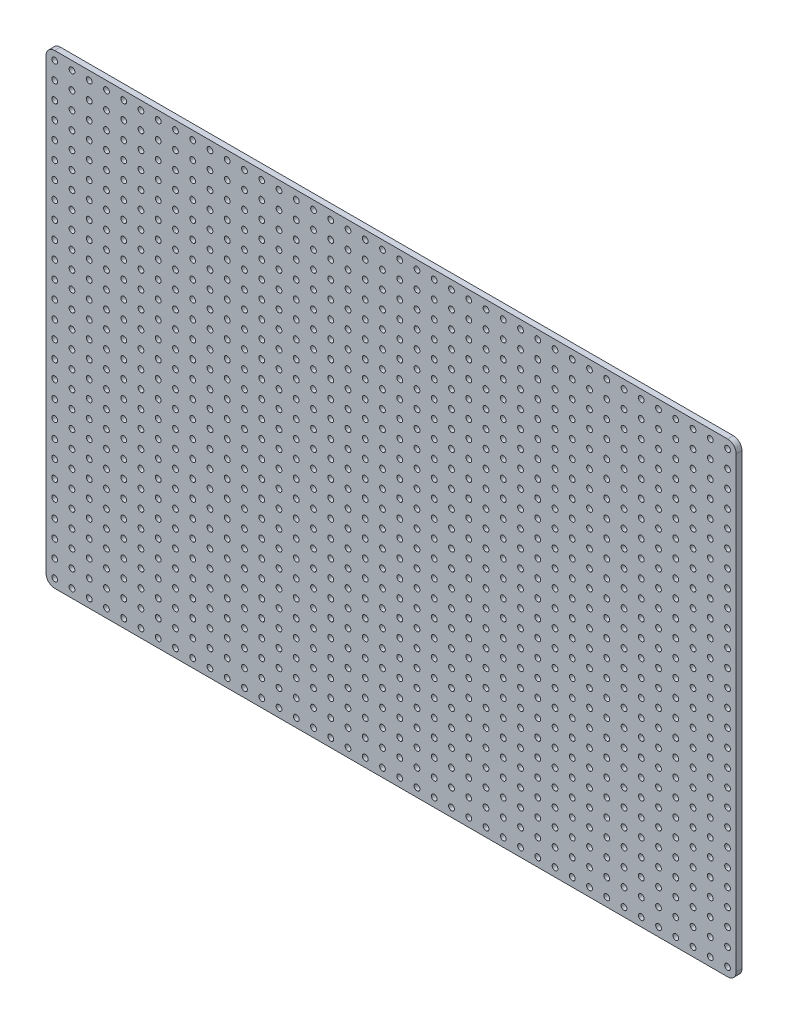
SolidWorks part; units mm, degrees
ref_plane "Alzado" through (0, 0, 0) normal (0, 0, 1) x (1, 0, 0)
ref_plane "Planta" through (0, 0, 0) normal (0, 1, 0) x (1, 0, 0)
ref_plane "Vista lateral" through (0, 0, 0) normal (1, 0, 0) x (0, 0, -1)
sketch "Model" plane through (0, 0, 0) normal (0, 0, 1) x (1, 0, 0)
  line L0 (256.4291, 489.7422) -> (607.4291, 489.7422)
  line L1 (256.4291, 246.7422) -> (607.4291, 246.7422)
  line L2 (251.9291, 251.2422) -> (251.9291, 485.2422)
  line L3 (611.9291, 485.2422) -> (611.9291, 251.2422)
  arc A0 (611.9291, 485.2422) -> (607.4291, 489.7422) centre (607.4291, 485.2422) ccw
  arc A1 (256.4291, 489.7422) -> (251.9291, 485.2422) centre (256.4291, 485.2422) ccw
  arc A2 (607.4291, 246.7422) -> (611.9291, 251.2422) centre (607.4291, 251.2422) ccw
  arc A3 (251.9291, 251.2422) -> (256.4291, 246.7422) centre (256.4291, 251.2422) ccw
  circle A4 centre (256.4291, 485.2422) radius 1.5
  circle A5 centre (256.4291, 476.2422) radius 1.5
  circle A6 centre (256.4291, 467.2422) radius 1.5
  circle A7 centre (256.4291, 458.2422) radius 1.5
  circle A8 centre (256.4291, 449.2422) radius 1.5
  circle A9 centre (256.4291, 440.2422) radius 1.5
  circle A10 centre (256.4291, 431.2422) radius 1.5
  circle A11 centre (256.4291, 422.2422) radius 1.5
  circle A12 centre (256.4291, 413.2422) radius 1.5
  circle A13 centre (256.4291, 404.2422) radius 1.5
  circle A14 centre (256.4291, 395.2422) radius 1.5
  circle A15 centre (256.4291, 386.2422) radius 1.5
  circle A16 centre (256.4291, 377.2422) radius 1.5
  circle A17 centre (256.4291, 368.2422) radius 1.5
  circle A18 centre (256.4291, 359.2422) radius 1.5
  circle A19 centre (256.4291, 350.2422) radius 1.5
  circle A20 centre (256.4291, 341.2422) radius 1.5
  circle A21 centre (256.4291, 332.2422) radius 1.5
  circle A22 centre (256.4291, 323.2422) radius 1.5
  circle A23 centre (256.4291, 314.2422) radius 1.5
  circle A24 centre (256.4291, 305.2422) radius 1.5
  circle A25 centre (265.4291, 485.2422) radius 1.5
  circle A26 centre (265.4291, 476.2422) radius 1.5
  circle A27 centre (265.4291, 467.2422) radius 1.5
  circle A28 centre (265.4291, 458.2422) radius 1.5
  circle A29 centre (265.4291, 449.2422) radius 1.5
  circle A30 centre (265.4291, 440.2422) radius 1.5
  circle A31 centre (265.4291, 431.2422) radius 1.5
  circle A32 centre (265.4291, 422.2422) radius 1.5
  circle A33 centre (265.4291, 413.2422) radius 1.5
  circle A34 centre (265.4291, 404.2422) radius 1.5
  circle A35 centre (265.4291, 395.2422) radius 1.5
  circle A36 centre (265.4291, 386.2422) radius 1.5
  circle A37 centre (265.4291, 377.2422) radius 1.5
  circle A38 centre (265.4291, 368.2422) radius 1.5
  circle A39 centre (265.4291, 359.2422) radius 1.5
  circle A40 centre (265.4291, 350.2422) radius 1.5
  circle A41 centre (265.4291, 341.2422) radius 1.5
  circle A42 centre (265.4291, 332.2422) radius 1.5
  circle A43 centre (265.4291, 323.2422) radius 1.5
  circle A44 centre (265.4291, 314.2422) radius 1.5
  circle A45 centre (265.4291, 305.2422) radius 1.5
  circle A46 centre (274.4291, 485.2422) radius 1.5
  circle A47 centre (274.4291, 476.2422) radius 1.5
  circle A48 centre (274.4291, 467.2422) radius 1.5
  circle A49 centre (274.4291, 458.2422) radius 1.5
  circle A50 centre (274.4291, 449.2422) radius 1.5
  circle A51 centre (274.4291, 440.2422) radius 1.5
  circle A52 centre (274.4291, 431.2422) radius 1.5
  circle A53 centre (274.4291, 422.2422) radius 1.5
  circle A54 centre (274.4291, 413.2422) radius 1.5
  circle A55 centre (274.4291, 404.2422) radius 1.5
  circle A56 centre (274.4291, 395.2422) radius 1.5
  circle A57 centre (274.4291, 386.2422) radius 1.5
  circle A58 centre (274.4291, 377.2422) radius 1.5
  circle A59 centre (274.4291, 368.2422) radius 1.5
  circle A60 centre (274.4291, 359.2422) radius 1.5
  circle A61 centre (274.4291, 350.2422) radius 1.5
  circle A62 centre (274.4291, 341.2422) radius 1.5
  circle A63 centre (274.4291, 332.2422) radius 1.5
  circle A64 centre (274.4291, 323.2422) radius 1.5
  circle A65 centre (274.4291, 314.2422) radius 1.5
  circle A66 centre (274.4291, 305.2422) radius 1.5
  circle A67 centre (283.4291, 485.2422) radius 1.5
  circle A68 centre (283.4291, 476.2422) radius 1.5
  circle A69 centre (283.4291, 467.2422) radius 1.5
  circle A70 centre (283.4291, 458.2422) radius 1.5
  circle A71 centre (283.4291, 449.2422) radius 1.5
  circle A72 centre (283.4291, 440.2422) radius 1.5
  circle A73 centre (283.4291, 431.2422) radius 1.5
  circle A74 centre (283.4291, 422.2422) radius 1.5
  circle A75 centre (283.4291, 413.2422) radius 1.5
  circle A76 centre (283.4291, 404.2422) radius 1.5
  circle A77 centre (283.4291, 395.2422) radius 1.5
  circle A78 centre (283.4291, 386.2422) radius 1.5
  circle A79 centre (283.4291, 377.2422) radius 1.5
  circle A80 centre (283.4291, 368.2422) radius 1.5
  circle A81 centre (283.4291, 359.2422) radius 1.5
  circle A82 centre (283.4291, 350.2422) radius 1.5
  circle A83 centre (283.4291, 341.2422) radius 1.5
  circle A84 centre (283.4291, 332.2422) radius 1.5
  circle A85 centre (283.4291, 323.2422) radius 1.5
  circle A86 centre (283.4291, 314.2422) radius 1.5
  circle A87 centre (283.4291, 305.2422) radius 1.5
  circle A88 centre (292.4291, 485.2422) radius 1.5
  circle A89 centre (292.4291, 476.2422) radius 1.5
  circle A90 centre (292.4291, 467.2422) radius 1.5
  circle A91 centre (292.4291, 458.2422) radius 1.5
  circle A92 centre (292.4291, 449.2422) radius 1.5
  circle A93 centre (292.4291, 440.2422) radius 1.5
  circle A94 centre (292.4291, 431.2422) radius 1.5
  circle A95 centre (292.4291, 422.2422) radius 1.5
  circle A96 centre (292.4291, 413.2422) radius 1.5
  circle A97 centre (292.4291, 404.2422) radius 1.5
  circle A98 centre (292.4291, 395.2422) radius 1.5
  circle A99 centre (292.4291, 386.2422) radius 1.5
  circle A100 centre (292.4291, 377.2422) radius 1.5
  circle A101 centre (292.4291, 368.2422) radius 1.5
  circle A102 centre (292.4291, 359.2422) radius 1.5
  circle A103 centre (292.4291, 350.2422) radius 1.5
  circle A104 centre (292.4291, 341.2422) radius 1.5
  circle A105 centre (292.4291, 332.2422) radius 1.5
  circle A106 centre (292.4291, 323.2422) radius 1.5
  circle A107 centre (292.4291, 314.2422) radius 1.5
  circle A108 centre (292.4291, 305.2422) radius 1.5
  circle A109 centre (301.4291, 485.2422) radius 1.5
  circle A110 centre (301.4291, 476.2422) radius 1.5
  circle A111 centre (301.4291, 467.2422) radius 1.5
  circle A112 centre (301.4291, 458.2422) radius 1.5
  circle A113 centre (301.4291, 449.2422) radius 1.5
  circle A114 centre (301.4291, 440.2422) radius 1.5
  circle A115 centre (301.4291, 431.2422) radius 1.5
  circle A116 centre (301.4291, 422.2422) radius 1.5
  circle A117 centre (301.4291, 413.2422) radius 1.5
  circle A118 centre (301.4291, 404.2422) radius 1.5
  circle A119 centre (301.4291, 395.2422) radius 1.5
  circle A120 centre (301.4291, 386.2422) radius 1.5
  circle A121 centre (301.4291, 377.2422) radius 1.5
  circle A122 centre (301.4291, 368.2422) radius 1.5
  circle A123 centre (301.4291, 359.2422) radius 1.5
  circle A124 centre (301.4291, 350.2422) radius 1.5
  circle A125 centre (301.4291, 341.2422) radius 1.5
  circle A126 centre (301.4291, 332.2422) radius 1.5
  circle A127 centre (301.4291, 323.2422) radius 1.5
  circle A128 centre (301.4291, 314.2422) radius 1.5
  circle A129 centre (301.4291, 305.2422) radius 1.5
  circle A130 centre (310.4291, 485.2422) radius 1.5
  circle A131 centre (310.4291, 476.2422) radius 1.5
  circle A132 centre (310.4291, 467.2422) radius 1.5
  circle A133 centre (310.4291, 458.2422) radius 1.5
  circle A134 centre (310.4291, 449.2422) radius 1.5
  circle A135 centre (310.4291, 440.2422) radius 1.5
  circle A136 centre (310.4291, 431.2422) radius 1.5
  circle A137 centre (310.4291, 422.2422) radius 1.5
  circle A138 centre (310.4291, 413.2422) radius 1.5
  circle A139 centre (310.4291, 404.2422) radius 1.5
  circle A140 centre (310.4291, 395.2422) radius 1.5
  circle A141 centre (310.4291, 386.2422) radius 1.5
  circle A142 centre (310.4291, 377.2422) radius 1.5
  circle A143 centre (310.4291, 368.2422) radius 1.5
  circle A144 centre (310.4291, 359.2422) radius 1.5
  circle A145 centre (310.4291, 350.2422) radius 1.5
  circle A146 centre (310.4291, 341.2422) radius 1.5
  circle A147 centre (310.4291, 332.2422) radius 1.5
  circle A148 centre (310.4291, 323.2422) radius 1.5
  circle A149 centre (310.4291, 314.2422) radius 1.5
  circle A150 centre (310.4291, 305.2422) radius 1.5
  circle A151 centre (319.4291, 485.2422) radius 1.5
  circle A152 centre (319.4291, 476.2422) radius 1.5
  circle A153 centre (319.4291, 467.2422) radius 1.5
  circle A154 centre (319.4291, 458.2422) radius 1.5
  circle A155 centre (319.4291, 449.2422) radius 1.5
  circle A156 centre (319.4291, 440.2422) radius 1.5
  circle A157 centre (319.4291, 431.2422) radius 1.5
  circle A158 centre (319.4291, 422.2422) radius 1.5
  circle A159 centre (319.4291, 413.2422) radius 1.5
  circle A160 centre (319.4291, 404.2422) radius 1.5
  circle A161 centre (319.4291, 395.2422) radius 1.5
  circle A162 centre (319.4291, 386.2422) radius 1.5
  circle A163 centre (319.4291, 377.2422) radius 1.5
  circle A164 centre (319.4291, 368.2422) radius 1.5
  circle A165 centre (319.4291, 359.2422) radius 1.5
  circle A166 centre (319.4291, 350.2422) radius 1.5
  circle A167 centre (319.4291, 341.2422) radius 1.5
  circle A168 centre (319.4291, 332.2422) radius 1.5
  circle A169 centre (319.4291, 323.2422) radius 1.5
  circle A170 centre (319.4291, 314.2422) radius 1.5
  circle A171 centre (319.4291, 305.2422) radius 1.5
  circle A172 centre (328.4291, 485.2422) radius 1.5
  circle A173 centre (328.4291, 476.2422) radius 1.5
  circle A174 centre (328.4291, 467.2422) radius 1.5
  circle A175 centre (328.4291, 458.2422) radius 1.5
  circle A176 centre (328.4291, 449.2422) radius 1.5
  circle A177 centre (328.4291, 440.2422) radius 1.5
  circle A178 centre (328.4291, 431.2422) radius 1.5
  circle A179 centre (328.4291, 422.2422) radius 1.5
  circle A180 centre (328.4291, 413.2422) radius 1.5
  circle A181 centre (328.4291, 404.2422) radius 1.5
  circle A182 centre (328.4291, 395.2422) radius 1.5
  circle A183 centre (328.4291, 386.2422) radius 1.5
  circle A184 centre (328.4291, 377.2422) radius 1.5
  circle A185 centre (328.4291, 368.2422) radius 1.5
  circle A186 centre (328.4291, 359.2422) radius 1.5
  circle A187 centre (328.4291, 350.2422) radius 1.5
  circle A188 centre (328.4291, 341.2422) radius 1.5
  circle A189 centre (328.4291, 332.2422) radius 1.5
  circle A190 centre (328.4291, 323.2422) radius 1.5
  circle A191 centre (328.4291, 314.2422) radius 1.5
  circle A192 centre (328.4291, 305.2422) radius 1.5
  circle A193 centre (337.4291, 485.2422) radius 1.5
  circle A194 centre (337.4291, 476.2422) radius 1.5
  circle A195 centre (337.4291, 467.2422) radius 1.5
  circle A196 centre (337.4291, 458.2422) radius 1.5
  circle A197 centre (337.4291, 449.2422) radius 1.5
  circle A198 centre (337.4291, 440.2422) radius 1.5
  circle A199 centre (337.4291, 431.2422) radius 1.5
  circle A200 centre (337.4291, 422.2422) radius 1.5
  circle A201 centre (337.4291, 413.2422) radius 1.5
  circle A202 centre (337.4291, 404.2422) radius 1.5
  circle A203 centre (337.4291, 395.2422) radius 1.5
  circle A204 centre (337.4291, 386.2422) radius 1.5
  circle A205 centre (337.4291, 377.2422) radius 1.5
  circle A206 centre (337.4291, 368.2422) radius 1.5
  circle A207 centre (337.4291, 359.2422) radius 1.5
  circle A208 centre (337.4291, 350.2422) radius 1.5
  circle A209 centre (337.4291, 341.2422) radius 1.5
  circle A210 centre (337.4291, 332.2422) radius 1.5
  circle A211 centre (337.4291, 323.2422) radius 1.5
  circle A212 centre (337.4291, 314.2422) radius 1.5
  circle A213 centre (337.4291, 305.2422) radius 1.5
  circle A214 centre (346.4291, 485.2422) radius 1.5
  circle A215 centre (346.4291, 476.2422) radius 1.5
  circle A216 centre (346.4291, 467.2422) radius 1.5
  circle A217 centre (346.4291, 458.2422) radius 1.5
  circle A218 centre (346.4291, 449.2422) radius 1.5
  circle A219 centre (346.4291, 440.2422) radius 1.5
  circle A220 centre (346.4291, 431.2422) radius 1.5
  circle A221 centre (346.4291, 422.2422) radius 1.5
  circle A222 centre (346.4291, 413.2422) radius 1.5
  circle A223 centre (346.4291, 404.2422) radius 1.5
  circle A224 centre (346.4291, 395.2422) radius 1.5
  circle A225 centre (346.4291, 386.2422) radius 1.5
  circle A226 centre (346.4291, 377.2422) radius 1.5
  circle A227 centre (346.4291, 368.2422) radius 1.5
  circle A228 centre (346.4291, 359.2422) radius 1.5
  circle A229 centre (346.4291, 350.2422) radius 1.5
  circle A230 centre (346.4291, 341.2422) radius 1.5
  circle A231 centre (346.4291, 332.2422) radius 1.5
  circle A232 centre (346.4291, 323.2422) radius 1.5
  circle A233 centre (346.4291, 314.2422) radius 1.5
  circle A234 centre (346.4291, 305.2422) radius 1.5
  circle A235 centre (355.4291, 485.2422) radius 1.5
  circle A236 centre (355.4291, 476.2422) radius 1.5
  circle A237 centre (355.4291, 467.2422) radius 1.5
  circle A238 centre (355.4291, 458.2422) radius 1.5
  circle A239 centre (355.4291, 449.2422) radius 1.5
  circle A240 centre (355.4291, 440.2422) radius 1.5
  circle A241 centre (355.4291, 431.2422) radius 1.5
  circle A242 centre (355.4291, 422.2422) radius 1.5
  circle A243 centre (355.4291, 413.2422) radius 1.5
  circle A244 centre (355.4291, 404.2422) radius 1.5
  circle A245 centre (355.4291, 395.2422) radius 1.5
  circle A246 centre (355.4291, 386.2422) radius 1.5
  circle A247 centre (355.4291, 377.2422) radius 1.5
  circle A248 centre (355.4291, 368.2422) radius 1.5
  circle A249 centre (355.4291, 359.2422) radius 1.5
  circle A250 centre (355.4291, 350.2422) radius 1.5
  circle A251 centre (355.4291, 341.2422) radius 1.5
  circle A252 centre (355.4291, 332.2422) radius 1.5
  circle A253 centre (355.4291, 323.2422) radius 1.5
  circle A254 centre (355.4291, 314.2422) radius 1.5
  circle A255 centre (355.4291, 305.2422) radius 1.5
  circle A256 centre (364.4291, 485.2422) radius 1.5
  circle A257 centre (364.4291, 476.2422) radius 1.5
  circle A258 centre (364.4291, 467.2422) radius 1.5
  circle A259 centre (364.4291, 458.2422) radius 1.5
  circle A260 centre (364.4291, 449.2422) radius 1.5
  circle A261 centre (364.4291, 440.2422) radius 1.5
  circle A262 centre (364.4291, 431.2422) radius 1.5
  circle A263 centre (364.4291, 422.2422) radius 1.5
  circle A264 centre (364.4291, 413.2422) radius 1.5
  circle A265 centre (364.4291, 404.2422) radius 1.5
  circle A266 centre (364.4291, 395.2422) radius 1.5
  circle A267 centre (364.4291, 386.2422) radius 1.5
  circle A268 centre (364.4291, 377.2422) radius 1.5
  circle A269 centre (364.4291, 368.2422) radius 1.5
  circle A270 centre (364.4291, 359.2422) radius 1.5
  circle A271 centre (364.4291, 350.2422) radius 1.5
  circle A272 centre (364.4291, 341.2422) radius 1.5
  circle A273 centre (364.4291, 332.2422) radius 1.5
  circle A274 centre (364.4291, 323.2422) radius 1.5
  circle A275 centre (364.4291, 314.2422) radius 1.5
  circle A276 centre (364.4291, 305.2422) radius 1.5
  circle A277 centre (373.4291, 485.2422) radius 1.5
  circle A278 centre (373.4291, 476.2422) radius 1.5
  circle A279 centre (373.4291, 467.2422) radius 1.5
  circle A280 centre (373.4291, 458.2422) radius 1.5
  circle A281 centre (373.4291, 449.2422) radius 1.5
  circle A282 centre (373.4291, 440.2422) radius 1.5
  circle A283 centre (373.4291, 431.2422) radius 1.5
  circle A284 centre (373.4291, 422.2422) radius 1.5
  circle A285 centre (373.4291, 413.2422) radius 1.5
  circle A286 centre (373.4291, 404.2422) radius 1.5
  circle A287 centre (373.4291, 395.2422) radius 1.5
  circle A288 centre (373.4291, 386.2422) radius 1.5
  circle A289 centre (373.4291, 377.2422) radius 1.5
  circle A290 centre (373.4291, 368.2422) radius 1.5
  circle A291 centre (373.4291, 359.2422) radius 1.5
  circle A292 centre (373.4291, 350.2422) radius 1.5
  circle A293 centre (373.4291, 341.2422) radius 1.5
  circle A294 centre (373.4291, 332.2422) radius 1.5
  circle A295 centre (373.4291, 323.2422) radius 1.5
  circle A296 centre (373.4291, 314.2422) radius 1.5
  circle A297 centre (373.4291, 305.2422) radius 1.5
  circle A298 centre (382.4291, 485.2422) radius 1.5
  circle A299 centre (382.4291, 476.2422) radius 1.5
  circle A300 centre (382.4291, 467.2422) radius 1.5
  circle A301 centre (382.4291, 458.2422) radius 1.5
  circle A302 centre (382.4291, 449.2422) radius 1.5
  circle A303 centre (382.4291, 440.2422) radius 1.5
  circle A304 centre (382.4291, 431.2422) radius 1.5
  circle A305 centre (382.4291, 422.2422) radius 1.5
  circle A306 centre (382.4291, 413.2422) radius 1.5
  circle A307 centre (382.4291, 404.2422) radius 1.5
  circle A308 centre (382.4291, 395.2422) radius 1.5
  circle A309 centre (382.4291, 386.2422) radius 1.5
  circle A310 centre (382.4291, 377.2422) radius 1.5
  circle A311 centre (382.4291, 368.2422) radius 1.5
  circle A312 centre (382.4291, 359.2422) radius 1.5
  circle A313 centre (382.4291, 350.2422) radius 1.5
  circle A314 centre (382.4291, 341.2422) radius 1.5
  circle A315 centre (382.4291, 332.2422) radius 1.5
  circle A316 centre (382.4291, 323.2422) radius 1.5
  circle A317 centre (382.4291, 314.2422) radius 1.5
  circle A318 centre (382.4291, 305.2422) radius 1.5
  circle A319 centre (391.4291, 485.2422) radius 1.5
  circle A320 centre (391.4291, 476.2422) radius 1.5
  circle A321 centre (391.4291, 467.2422) radius 1.5
  circle A322 centre (391.4291, 458.2422) radius 1.5
  circle A323 centre (391.4291, 449.2422) radius 1.5
  circle A324 centre (391.4291, 440.2422) radius 1.5
  circle A325 centre (391.4291, 431.2422) radius 1.5
  circle A326 centre (391.4291, 422.2422) radius 1.5
  circle A327 centre (391.4291, 413.2422) radius 1.5
  circle A328 centre (391.4291, 404.2422) radius 1.5
  circle A329 centre (391.4291, 395.2422) radius 1.5
  circle A330 centre (391.4291, 386.2422) radius 1.5
  circle A331 centre (391.4291, 377.2422) radius 1.5
  circle A332 centre (391.4291, 368.2422) radius 1.5
  circle A333 centre (391.4291, 359.2422) radius 1.5
  circle A334 centre (391.4291, 350.2422) radius 1.5
  circle A335 centre (391.4291, 341.2422) radius 1.5
  circle A336 centre (391.4291, 332.2422) radius 1.5
  circle A337 centre (391.4291, 323.2422) radius 1.5
  circle A338 centre (391.4291, 314.2422) radius 1.5
  circle A339 centre (391.4291, 305.2422) radius 1.5
  circle A340 centre (400.4291, 485.2422) radius 1.5
  circle A341 centre (400.4291, 476.2422) radius 1.5
  circle A342 centre (400.4291, 467.2422) radius 1.5
  circle A343 centre (400.4291, 458.2422) radius 1.5
  circle A344 centre (400.4291, 449.2422) radius 1.5
  circle A345 centre (400.4291, 440.2422) radius 1.5
  circle A346 centre (400.4291, 431.2422) radius 1.5
  circle A347 centre (400.4291, 422.2422) radius 1.5
  circle A348 centre (400.4291, 413.2422) radius 1.5
  circle A349 centre (400.4291, 404.2422) radius 1.5
  circle A350 centre (400.4291, 395.2422) radius 1.5
  circle A351 centre (400.4291, 386.2422) radius 1.5
  circle A352 centre (400.4291, 377.2422) radius 1.5
  circle A353 centre (400.4291, 368.2422) radius 1.5
  circle A354 centre (400.4291, 359.2422) radius 1.5
  circle A355 centre (400.4291, 350.2422) radius 1.5
  circle A356 centre (400.4291, 341.2422) radius 1.5
  circle A357 centre (400.4291, 332.2422) radius 1.5
  circle A358 centre (400.4291, 323.2422) radius 1.5
  circle A359 centre (400.4291, 314.2422) radius 1.5
  circle A360 centre (400.4291, 305.2422) radius 1.5
  circle A361 centre (409.4291, 485.2422) radius 1.5
  circle A362 centre (409.4291, 476.2422) radius 1.5
  circle A363 centre (409.4291, 467.2422) radius 1.5
  circle A364 centre (409.4291, 458.2422) radius 1.5
  circle A365 centre (409.4291, 449.2422) radius 1.5
  circle A366 centre (409.4291, 440.2422) radius 1.5
  circle A367 centre (409.4291, 431.2422) radius 1.5
  circle A368 centre (409.4291, 422.2422) radius 1.5
  circle A369 centre (409.4291, 413.2422) radius 1.5
  circle A370 centre (409.4291, 404.2422) radius 1.5
  circle A371 centre (409.4291, 395.2422) radius 1.5
  circle A372 centre (409.4291, 386.2422) radius 1.5
  circle A373 centre (409.4291, 377.2422) radius 1.5
  circle A374 centre (409.4291, 368.2422) radius 1.5
  circle A375 centre (409.4291, 359.2422) radius 1.5
  circle A376 centre (409.4291, 350.2422) radius 1.5
  circle A377 centre (409.4291, 341.2422) radius 1.5
  circle A378 centre (409.4291, 332.2422) radius 1.5
  circle A379 centre (409.4291, 323.2422) radius 1.5
  circle A380 centre (409.4291, 314.2422) radius 1.5
  circle A381 centre (409.4291, 305.2422) radius 1.5
  circle A382 centre (418.4291, 485.2422) radius 1.5
  circle A383 centre (418.4291, 476.2422) radius 1.5
  circle A384 centre (418.4291, 467.2422) radius 1.5
  circle A385 centre (418.4291, 458.2422) radius 1.5
  circle A386 centre (418.4291, 449.2422) radius 1.5
  circle A387 centre (418.4291, 440.2422) radius 1.5
  circle A388 centre (418.4291, 431.2422) radius 1.5
  circle A389 centre (418.4291, 422.2422) radius 1.5
  circle A390 centre (418.4291, 413.2422) radius 1.5
  circle A391 centre (418.4291, 404.2422) radius 1.5
  circle A392 centre (418.4291, 395.2422) radius 1.5
  circle A393 centre (418.4291, 386.2422) radius 1.5
  circle A394 centre (418.4291, 377.2422) radius 1.5
  circle A395 centre (418.4291, 368.2422) radius 1.5
  circle A396 centre (418.4291, 359.2422) radius 1.5
  circle A397 centre (418.4291, 350.2422) radius 1.5
  circle A398 centre (418.4291, 341.2422) radius 1.5
  circle A399 centre (418.4291, 332.2422) radius 1.5
  circle A400 centre (418.4291, 323.2422) radius 1.5
  circle A401 centre (418.4291, 314.2422) radius 1.5
  circle A402 centre (418.4291, 305.2422) radius 1.5
  circle A403 centre (427.4291, 485.2422) radius 1.5
  circle A404 centre (427.4291, 476.2422) radius 1.5
  circle A405 centre (427.4291, 467.2422) radius 1.5
  circle A406 centre (427.4291, 458.2422) radius 1.5
  circle A407 centre (427.4291, 449.2422) radius 1.5
  circle A408 centre (427.4291, 440.2422) radius 1.5
  circle A409 centre (427.4291, 431.2422) radius 1.5
  circle A410 centre (427.4291, 422.2422) radius 1.5
  circle A411 centre (427.4291, 413.2422) radius 1.5
  circle A412 centre (427.4291, 404.2422) radius 1.5
  circle A413 centre (427.4291, 395.2422) radius 1.5
  circle A414 centre (427.4291, 386.2422) radius 1.5
  circle A415 centre (427.4291, 377.2422) radius 1.5
  circle A416 centre (427.4291, 368.2422) radius 1.5
  circle A417 centre (427.4291, 359.2422) radius 1.5
  circle A418 centre (427.4291, 350.2422) radius 1.5
  circle A419 centre (427.4291, 341.2422) radius 1.5
  circle A420 centre (427.4291, 332.2422) radius 1.5
  circle A421 centre (427.4291, 323.2422) radius 1.5
  circle A422 centre (427.4291, 314.2422) radius 1.5
  circle A423 centre (427.4291, 305.2422) radius 1.5
  circle A424 centre (436.4291, 485.2422) radius 1.5
  circle A425 centre (436.4291, 476.2422) radius 1.5
  circle A426 centre (436.4291, 467.2422) radius 1.5
  circle A427 centre (436.4291, 458.2422) radius 1.5
  circle A428 centre (436.4291, 449.2422) radius 1.5
  circle A429 centre (436.4291, 440.2422) radius 1.5
  circle A430 centre (436.4291, 431.2422) radius 1.5
  circle A431 centre (436.4291, 422.2422) radius 1.5
  circle A432 centre (436.4291, 413.2422) radius 1.5
  circle A433 centre (436.4291, 404.2422) radius 1.5
  circle A434 centre (436.4291, 395.2422) radius 1.5
  circle A435 centre (436.4291, 386.2422) radius 1.5
  circle A436 centre (436.4291, 377.2422) radius 1.5
  circle A437 centre (436.4291, 368.2422) radius 1.5
  circle A438 centre (436.4291, 359.2422) radius 1.5
  circle A439 centre (436.4291, 350.2422) radius 1.5
  circle A440 centre (436.4291, 341.2422) radius 1.5
  circle A441 centre (436.4291, 332.2422) radius 1.5
  circle A442 centre (436.4291, 323.2422) radius 1.5
  circle A443 centre (436.4291, 314.2422) radius 1.5
  circle A444 centre (436.4291, 305.2422) radius 1.5
  circle A445 centre (445.4291, 485.2422) radius 1.5
  circle A446 centre (445.4291, 476.2422) radius 1.5
  circle A447 centre (445.4291, 467.2422) radius 1.5
  circle A448 centre (445.4291, 458.2422) radius 1.5
  circle A449 centre (445.4291, 449.2422) radius 1.5
  circle A450 centre (445.4291, 440.2422) radius 1.5
  circle A451 centre (445.4291, 431.2422) radius 1.5
  circle A452 centre (445.4291, 422.2422) radius 1.5
  circle A453 centre (445.4291, 413.2422) radius 1.5
  circle A454 centre (445.4291, 404.2422) radius 1.5
  circle A455 centre (445.4291, 395.2422) radius 1.5
  circle A456 centre (445.4291, 386.2422) radius 1.5
  circle A457 centre (445.4291, 377.2422) radius 1.5
  circle A458 centre (445.4291, 368.2422) radius 1.5
  circle A459 centre (445.4291, 359.2422) radius 1.5
  circle A460 centre (445.4291, 350.2422) radius 1.5
  circle A461 centre (445.4291, 341.2422) radius 1.5
  circle A462 centre (445.4291, 332.2422) radius 1.5
  circle A463 centre (445.4291, 323.2422) radius 1.5
  circle A464 centre (445.4291, 314.2422) radius 1.5
  circle A465 centre (445.4291, 305.2422) radius 1.5
  circle A466 centre (454.4291, 485.2422) radius 1.5
  circle A467 centre (454.4291, 476.2422) radius 1.5
  circle A468 centre (454.4291, 467.2422) radius 1.5
  circle A469 centre (454.4291, 458.2422) radius 1.5
  circle A470 centre (454.4291, 449.2422) radius 1.5
  circle A471 centre (454.4291, 440.2422) radius 1.5
  circle A472 centre (454.4291, 431.2422) radius 1.5
  circle A473 centre (454.4291, 422.2422) radius 1.5
  circle A474 centre (454.4291, 413.2422) radius 1.5
  circle A475 centre (454.4291, 404.2422) radius 1.5
  circle A476 centre (454.4291, 395.2422) radius 1.5
  circle A477 centre (454.4291, 386.2422) radius 1.5
  circle A478 centre (454.4291, 377.2422) radius 1.5
  circle A479 centre (454.4291, 368.2422) radius 1.5
  circle A480 centre (454.4291, 359.2422) radius 1.5
  circle A481 centre (454.4291, 350.2422) radius 1.5
  circle A482 centre (454.4291, 341.2422) radius 1.5
  circle A483 centre (454.4291, 332.2422) radius 1.5
  circle A484 centre (454.4291, 323.2422) radius 1.5
  circle A485 centre (454.4291, 314.2422) radius 1.5
  circle A486 centre (454.4291, 305.2422) radius 1.5
  circle A487 centre (463.4291, 485.2422) radius 1.5
  circle A488 centre (463.4291, 476.2422) radius 1.5
  circle A489 centre (463.4291, 467.2422) radius 1.5
  circle A490 centre (463.4291, 458.2422) radius 1.5
  circle A491 centre (463.4291, 449.2422) radius 1.5
  circle A492 centre (463.4291, 440.2422) radius 1.5
  circle A493 centre (463.4291, 431.2422) radius 1.5
  circle A494 centre (463.4291, 422.2422) radius 1.5
  circle A495 centre (463.4291, 413.2422) radius 1.5
  circle A496 centre (463.4291, 404.2422) radius 1.5
  circle A497 centre (463.4291, 395.2422) radius 1.5
  circle A498 centre (463.4291, 386.2422) radius 1.5
  circle A499 centre (463.4291, 377.2422) radius 1.5
  circle A500 centre (463.4291, 368.2422) radius 1.5
  circle A501 centre (463.4291, 359.2422) radius 1.5
  circle A502 centre (463.4291, 350.2422) radius 1.5
  circle A503 centre (463.4291, 341.2422) radius 1.5
  circle A504 centre (463.4291, 332.2422) radius 1.5
  circle A505 centre (463.4291, 323.2422) radius 1.5
  circle A506 centre (463.4291, 314.2422) radius 1.5
  circle A507 centre (463.4291, 305.2422) radius 1.5
  circle A508 centre (472.4291, 485.2422) radius 1.5
  circle A509 centre (472.4291, 476.2422) radius 1.5
  circle A510 centre (472.4291, 467.2422) radius 1.5
  circle A511 centre (472.4291, 458.2422) radius 1.5
  circle A512 centre (472.4291, 449.2422) radius 1.5
  circle A513 centre (472.4291, 440.2422) radius 1.5
  circle A514 centre (472.4291, 431.2422) radius 1.5
  circle A515 centre (472.4291, 422.2422) radius 1.5
  circle A516 centre (472.4291, 413.2422) radius 1.5
  circle A517 centre (472.4291, 404.2422) radius 1.5
  circle A518 centre (472.4291, 395.2422) radius 1.5
  circle A519 centre (472.4291, 386.2422) radius 1.5
  circle A520 centre (472.4291, 377.2422) radius 1.5
  circle A521 centre (472.4291, 368.2422) radius 1.5
  circle A522 centre (472.4291, 359.2422) radius 1.5
  circle A523 centre (472.4291, 350.2422) radius 1.5
  circle A524 centre (472.4291, 341.2422) radius 1.5
  circle A525 centre (472.4291, 332.2422) radius 1.5
  circle A526 centre (472.4291, 323.2422) radius 1.5
  circle A527 centre (472.4291, 314.2422) radius 1.5
  circle A528 centre (472.4291, 305.2422) radius 1.5
  circle A529 centre (481.4291, 485.2422) radius 1.5
  circle A530 centre (481.4291, 476.2422) radius 1.5
  circle A531 centre (481.4291, 467.2422) radius 1.5
  circle A532 centre (481.4291, 458.2422) radius 1.5
  circle A533 centre (481.4291, 449.2422) radius 1.5
  circle A534 centre (481.4291, 440.2422) radius 1.5
  circle A535 centre (481.4291, 431.2422) radius 1.5
  circle A536 centre (481.4291, 422.2422) radius 1.5
  circle A537 centre (481.4291, 413.2422) radius 1.5
  circle A538 centre (481.4291, 404.2422) radius 1.5
  circle A539 centre (481.4291, 395.2422) radius 1.5
  circle A540 centre (481.4291, 386.2422) radius 1.5
  circle A541 centre (481.4291, 377.2422) radius 1.5
  circle A542 centre (481.4291, 368.2422) radius 1.5
  circle A543 centre (481.4291, 359.2422) radius 1.5
  circle A544 centre (481.4291, 350.2422) radius 1.5
  circle A545 centre (481.4291, 341.2422) radius 1.5
  circle A546 centre (481.4291, 332.2422) radius 1.5
  circle A547 centre (481.4291, 323.2422) radius 1.5
  circle A548 centre (481.4291, 314.2422) radius 1.5
  circle A549 centre (481.4291, 305.2422) radius 1.5
  circle A550 centre (490.4291, 485.2422) radius 1.5
  circle A551 centre (490.4291, 476.2422) radius 1.5
  circle A552 centre (490.4291, 467.2422) radius 1.5
  circle A553 centre (490.4291, 458.2422) radius 1.5
  circle A554 centre (490.4291, 449.2422) radius 1.5
  circle A555 centre (490.4291, 440.2422) radius 1.5
  circle A556 centre (490.4291, 431.2422) radius 1.5
  circle A557 centre (490.4291, 422.2422) radius 1.5
  circle A558 centre (490.4291, 413.2422) radius 1.5
  circle A559 centre (490.4291, 404.2422) radius 1.5
  circle A560 centre (490.4291, 395.2422) radius 1.5
  circle A561 centre (490.4291, 386.2422) radius 1.5
  circle A562 centre (490.4291, 377.2422) radius 1.5
  circle A563 centre (490.4291, 368.2422) radius 1.5
  circle A564 centre (490.4291, 359.2422) radius 1.5
  circle A565 centre (490.4291, 350.2422) radius 1.5
  circle A566 centre (490.4291, 341.2422) radius 1.5
  circle A567 centre (490.4291, 332.2422) radius 1.5
  circle A568 centre (490.4291, 323.2422) radius 1.5
  circle A569 centre (490.4291, 314.2422) radius 1.5
  circle A570 centre (490.4291, 305.2422) radius 1.5
  circle A571 centre (499.4291, 485.2422) radius 1.5
  circle A572 centre (499.4291, 476.2422) radius 1.5
  circle A573 centre (499.4291, 467.2422) radius 1.5
  circle A574 centre (499.4291, 458.2422) radius 1.5
  circle A575 centre (499.4291, 449.2422) radius 1.5
  circle A576 centre (499.4291, 440.2422) radius 1.5
  circle A577 centre (499.4291, 431.2422) radius 1.5
  circle A578 centre (499.4291, 422.2422) radius 1.5
  circle A579 centre (499.4291, 413.2422) radius 1.5
  circle A580 centre (499.4291, 404.2422) radius 1.5
  circle A581 centre (499.4291, 395.2422) radius 1.5
  circle A582 centre (499.4291, 386.2422) radius 1.5
  circle A583 centre (499.4291, 377.2422) radius 1.5
  circle A584 centre (499.4291, 368.2422) radius 1.5
  circle A585 centre (499.4291, 359.2422) radius 1.5
  circle A586 centre (499.4291, 350.2422) radius 1.5
  circle A587 centre (499.4291, 341.2422) radius 1.5
  circle A588 centre (499.4291, 332.2422) radius 1.5
  circle A589 centre (499.4291, 323.2422) radius 1.5
  circle A590 centre (499.4291, 314.2422) radius 1.5
  circle A591 centre (499.4291, 305.2422) radius 1.5
  circle A592 centre (508.4291, 485.2422) radius 1.5
  circle A593 centre (508.4291, 476.2422) radius 1.5
  circle A594 centre (508.4291, 467.2422) radius 1.5
  circle A595 centre (508.4291, 458.2422) radius 1.5
  circle A596 centre (508.4291, 449.2422) radius 1.5
  circle A597 centre (508.4291, 440.2422) radius 1.5
  circle A598 centre (508.4291, 431.2422) radius 1.5
  circle A599 centre (508.4291, 422.2422) radius 1.5
  circle A600 centre (508.4291, 413.2422) radius 1.5
  circle A601 centre (508.4291, 404.2422) radius 1.5
  circle A602 centre (508.4291, 395.2422) radius 1.5
  circle A603 centre (508.4291, 386.2422) radius 1.5
  circle A604 centre (508.4291, 377.2422) radius 1.5
  circle A605 centre (508.4291, 368.2422) radius 1.5
  circle A606 centre (508.4291, 359.2422) radius 1.5
  circle A607 centre (508.4291, 350.2422) radius 1.5
  circle A608 centre (508.4291, 341.2422) radius 1.5
  circle A609 centre (508.4291, 332.2422) radius 1.5
  circle A610 centre (508.4291, 323.2422) radius 1.5
  circle A611 centre (508.4291, 314.2422) radius 1.5
  circle A612 centre (508.4291, 305.2422) radius 1.5
  circle A613 centre (517.4291, 485.2422) radius 1.5
  circle A614 centre (517.4291, 476.2422) radius 1.5
  circle A615 centre (517.4291, 467.2422) radius 1.5
  circle A616 centre (517.4291, 458.2422) radius 1.5
  circle A617 centre (517.4291, 449.2422) radius 1.5
  circle A618 centre (517.4291, 440.2422) radius 1.5
  circle A619 centre (517.4291, 431.2422) radius 1.5
  circle A620 centre (517.4291, 422.2422) radius 1.5
  circle A621 centre (517.4291, 413.2422) radius 1.5
  circle A622 centre (517.4291, 404.2422) radius 1.5
  circle A623 centre (517.4291, 395.2422) radius 1.5
  circle A624 centre (517.4291, 386.2422) radius 1.5
  circle A625 centre (517.4291, 377.2422) radius 1.5
  circle A626 centre (517.4291, 368.2422) radius 1.5
  circle A627 centre (517.4291, 359.2422) radius 1.5
  circle A628 centre (517.4291, 350.2422) radius 1.5
  circle A629 centre (517.4291, 341.2422) radius 1.5
  circle A630 centre (517.4291, 332.2422) radius 1.5
  circle A631 centre (517.4291, 323.2422) radius 1.5
  circle A632 centre (517.4291, 314.2422) radius 1.5
  circle A633 centre (517.4291, 305.2422) radius 1.5
  circle A634 centre (256.4291, 296.2422) radius 1.5
  circle A635 centre (256.4291, 287.2422) radius 1.5
  circle A636 centre (256.4291, 278.2422) radius 1.5
  circle A637 centre (265.4291, 296.2422) radius 1.5
  circle A638 centre (265.4291, 287.2422) radius 1.5
  circle A639 centre (265.4291, 278.2422) radius 1.5
  circle A640 centre (274.4291, 296.2422) radius 1.5
  circle A641 centre (274.4291, 287.2422) radius 1.5
  circle A642 centre (274.4291, 278.2422) radius 1.5
  circle A643 centre (283.4291, 296.2422) radius 1.5
  circle A644 centre (283.4291, 287.2422) radius 1.5
  circle A645 centre (283.4291, 278.2422) radius 1.5
  circle A646 centre (292.4291, 296.2422) radius 1.5
  circle A647 centre (292.4291, 287.2422) radius 1.5
  circle A648 centre (292.4291, 278.2422) radius 1.5
  circle A649 centre (301.4291, 296.2422) radius 1.5
  circle A650 centre (301.4291, 287.2422) radius 1.5
  circle A651 centre (301.4291, 278.2422) radius 1.5
  circle A652 centre (310.4291, 296.2422) radius 1.5
  circle A653 centre (310.4291, 287.2422) radius 1.5
  circle A654 centre (310.4291, 278.2422) radius 1.5
  circle A655 centre (319.4291, 296.2422) radius 1.5
  circle A656 centre (319.4291, 287.2422) radius 1.5
  circle A657 centre (319.4291, 278.2422) radius 1.5
  circle A658 centre (328.4291, 296.2422) radius 1.5
  circle A659 centre (328.4291, 287.2422) radius 1.5
  circle A660 centre (328.4291, 278.2422) radius 1.5
  circle A661 centre (337.4291, 296.2422) radius 1.5
  circle A662 centre (337.4291, 287.2422) radius 1.5
  circle A663 centre (337.4291, 278.2422) radius 1.5
  circle A664 centre (346.4291, 296.2422) radius 1.5
  circle A665 centre (346.4291, 287.2422) radius 1.5
  circle A666 centre (346.4291, 278.2422) radius 1.5
  circle A667 centre (355.4291, 296.2422) radius 1.5
  circle A668 centre (355.4291, 287.2422) radius 1.5
  circle A669 centre (355.4291, 278.2422) radius 1.5
  circle A670 centre (364.4291, 296.2422) radius 1.5
  circle A671 centre (364.4291, 287.2422) radius 1.5
  circle A672 centre (364.4291, 278.2422) radius 1.5
  circle A673 centre (373.4291, 296.2422) radius 1.5
  circle A674 centre (373.4291, 287.2422) radius 1.5
  circle A675 centre (373.4291, 278.2422) radius 1.5
  circle A676 centre (382.4291, 296.2422) radius 1.5
  circle A677 centre (382.4291, 287.2422) radius 1.5
  circle A678 centre (382.4291, 278.2422) radius 1.5
  circle A679 centre (391.4291, 296.2422) radius 1.5
  circle A680 centre (391.4291, 287.2422) radius 1.5
  circle A681 centre (391.4291, 278.2422) radius 1.5
  circle A682 centre (400.4291, 296.2422) radius 1.5
  circle A683 centre (400.4291, 287.2422) radius 1.5
  circle A684 centre (400.4291, 278.2422) radius 1.5
  circle A685 centre (409.4291, 296.2422) radius 1.5
  circle A686 centre (409.4291, 287.2422) radius 1.5
  circle A687 centre (409.4291, 278.2422) radius 1.5
  circle A688 centre (418.4291, 296.2422) radius 1.5
  circle A689 centre (418.4291, 287.2422) radius 1.5
  circle A690 centre (418.4291, 278.2422) radius 1.5
  circle A691 centre (427.4291, 296.2422) radius 1.5
  circle A692 centre (427.4291, 287.2422) radius 1.5
  circle A693 centre (427.4291, 278.2422) radius 1.5
  circle A694 centre (436.4291, 296.2422) radius 1.5
  circle A695 centre (436.4291, 287.2422) radius 1.5
  circle A696 centre (436.4291, 278.2422) radius 1.5
  circle A697 centre (445.4291, 296.2422) radius 1.5
  circle A698 centre (445.4291, 287.2422) radius 1.5
  circle A699 centre (445.4291, 278.2422) radius 1.5
  circle A700 centre (454.4291, 296.2422) radius 1.5
  circle A701 centre (454.4291, 287.2422) radius 1.5
  circle A702 centre (454.4291, 278.2422) radius 1.5
  circle A703 centre (463.4291, 296.2422) radius 1.5
  circle A704 centre (463.4291, 287.2422) radius 1.5
  circle A705 centre (463.4291, 278.2422) radius 1.5
  circle A706 centre (472.4291, 296.2422) radius 1.5
  circle A707 centre (472.4291, 287.2422) radius 1.5
  circle A708 centre (472.4291, 278.2422) radius 1.5
  circle A709 centre (481.4291, 296.2422) radius 1.5
  circle A710 centre (481.4291, 287.2422) radius 1.5
  circle A711 centre (481.4291, 278.2422) radius 1.5
  circle A712 centre (490.4291, 296.2422) radius 1.5
  circle A713 centre (490.4291, 287.2422) radius 1.5
  circle A714 centre (490.4291, 278.2422) radius 1.5
  circle A715 centre (499.4291, 296.2422) radius 1.5
  circle A716 centre (499.4291, 287.2422) radius 1.5
  circle A717 centre (499.4291, 278.2422) radius 1.5
  circle A718 centre (508.4291, 296.2422) radius 1.5
  circle A719 centre (508.4291, 287.2422) radius 1.5
  circle A720 centre (508.4291, 278.2422) radius 1.5
  circle A721 centre (517.4291, 296.2422) radius 1.5
  circle A722 centre (517.4291, 287.2422) radius 1.5
  circle A723 centre (517.4291, 278.2422) radius 1.5
  circle A724 centre (256.4291, 269.2422) radius 1.5
  circle A725 centre (256.4291, 260.2422) radius 1.5
  circle A726 centre (256.4291, 251.2422) radius 1.5
  circle A727 centre (265.4291, 269.2422) radius 1.5
  circle A728 centre (265.4291, 260.2422) radius 1.5
  circle A729 centre (265.4291, 251.2422) radius 1.5
  circle A730 centre (274.4291, 269.2422) radius 1.5
  circle A731 centre (274.4291, 260.2422) radius 1.5
  circle A732 centre (274.4291, 251.2422) radius 1.5
  circle A733 centre (283.4291, 269.2422) radius 1.5
  circle A734 centre (283.4291, 260.2422) radius 1.5
  circle A735 centre (283.4291, 251.2422) radius 1.5
  circle A736 centre (292.4291, 269.2422) radius 1.5
  circle A737 centre (292.4291, 260.2422) radius 1.5
  circle A738 centre (292.4291, 251.2422) radius 1.5
  circle A739 centre (301.4291, 269.2422) radius 1.5
  circle A740 centre (301.4291, 260.2422) radius 1.5
  circle A741 centre (301.4291, 251.2422) radius 1.5
  circle A742 centre (310.4291, 269.2422) radius 1.5
  circle A743 centre (310.4291, 260.2422) radius 1.5
  circle A744 centre (310.4291, 251.2422) radius 1.5
  circle A745 centre (319.4291, 269.2422) radius 1.5
  circle A746 centre (319.4291, 260.2422) radius 1.5
  circle A747 centre (319.4291, 251.2422) radius 1.5
  circle A748 centre (328.4291, 269.2422) radius 1.5
  circle A749 centre (328.4291, 260.2422) radius 1.5
  circle A750 centre (328.4291, 251.2422) radius 1.5
  circle A751 centre (337.4291, 269.2422) radius 1.5
  circle A752 centre (337.4291, 260.2422) radius 1.5
  circle A753 centre (337.4291, 251.2422) radius 1.5
  circle A754 centre (346.4291, 269.2422) radius 1.5
  circle A755 centre (346.4291, 260.2422) radius 1.5
  circle A756 centre (346.4291, 251.2422) radius 1.5
  circle A757 centre (355.4291, 269.2422) radius 1.5
  circle A758 centre (355.4291, 260.2422) radius 1.5
  circle A759 centre (355.4291, 251.2422) radius 1.5
  circle A760 centre (364.4291, 269.2422) radius 1.5
  circle A761 centre (364.4291, 260.2422) radius 1.5
  circle A762 centre (364.4291, 251.2422) radius 1.5
  circle A763 centre (373.4291, 269.2422) radius 1.5
  circle A764 centre (373.4291, 260.2422) radius 1.5
  circle A765 centre (373.4291, 251.2422) radius 1.5
  circle A766 centre (382.4291, 269.2422) radius 1.5
  circle A767 centre (382.4291, 260.2422) radius 1.5
  circle A768 centre (382.4291, 251.2422) radius 1.5
  circle A769 centre (391.4291, 269.2422) radius 1.5
  circle A770 centre (391.4291, 260.2422) radius 1.5
  circle A771 centre (391.4291, 251.2422) radius 1.5
  circle A772 centre (400.4291, 269.2422) radius 1.5
  circle A773 centre (400.4291, 260.2422) radius 1.5
  circle A774 centre (400.4291, 251.2422) radius 1.5
  circle A775 centre (409.4291, 269.2422) radius 1.5
  circle A776 centre (409.4291, 260.2422) radius 1.5
  circle A777 centre (409.4291, 251.2422) radius 1.5
  circle A778 centre (418.4291, 269.2422) radius 1.5
  circle A779 centre (418.4291, 260.2422) radius 1.5
  circle A780 centre (418.4291, 251.2422) radius 1.5
  circle A781 centre (427.4291, 269.2422) radius 1.5
  circle A782 centre (427.4291, 260.2422) radius 1.5
  circle A783 centre (427.4291, 251.2422) radius 1.5
  circle A784 centre (436.4291, 269.2422) radius 1.5
  circle A785 centre (436.4291, 260.2422) radius 1.5
  circle A786 centre (436.4291, 251.2422) radius 1.5
  circle A787 centre (445.4291, 269.2422) radius 1.5
  circle A788 centre (445.4291, 260.2422) radius 1.5
  circle A789 centre (445.4291, 251.2422) radius 1.5
  circle A790 centre (454.4291, 269.2422) radius 1.5
  circle A791 centre (454.4291, 260.2422) radius 1.5
  circle A792 centre (454.4291, 251.2422) radius 1.5
  circle A793 centre (463.4291, 269.2422) radius 1.5
  circle A794 centre (463.4291, 260.2422) radius 1.5
  circle A795 centre (463.4291, 251.2422) radius 1.5
  circle A796 centre (472.4291, 269.2422) radius 1.5
  circle A797 centre (472.4291, 260.2422) radius 1.5
  circle A798 centre (472.4291, 251.2422) radius 1.5
  circle A799 centre (481.4291, 269.2422) radius 1.5
  circle A800 centre (481.4291, 260.2422) radius 1.5
  circle A801 centre (481.4291, 251.2422) radius 1.5
  circle A802 centre (490.4291, 269.2422) radius 1.5
  circle A803 centre (490.4291, 260.2422) radius 1.5
  circle A804 centre (490.4291, 251.2422) radius 1.5
  circle A805 centre (499.4291, 269.2422) radius 1.5
  circle A806 centre (499.4291, 260.2422) radius 1.5
  circle A807 centre (499.4291, 251.2422) radius 1.5
  circle A808 centre (508.4291, 269.2422) radius 1.5
  circle A809 centre (508.4291, 260.2422) radius 1.5
  circle A810 centre (508.4291, 251.2422) radius 1.5
  circle A811 centre (517.4291, 269.2422) radius 1.5
  circle A812 centre (517.4291, 260.2422) radius 1.5
  circle A813 centre (517.4291, 251.2422) radius 1.5
  circle A814 centre (526.4291, 485.2422) radius 1.5
  circle A815 centre (526.4291, 476.2422) radius 1.5
  circle A816 centre (526.4291, 467.2422) radius 1.5
  circle A817 centre (526.4291, 458.2422) radius 1.5
  circle A818 centre (526.4291, 449.2422) radius 1.5
  circle A819 centre (526.4291, 440.2422) radius 1.5
  circle A820 centre (526.4291, 431.2422) radius 1.5
  circle A821 centre (526.4291, 422.2422) radius 1.5
  circle A822 centre (526.4291, 413.2422) radius 1.5
  circle A823 centre (526.4291, 404.2422) radius 1.5
  circle A824 centre (526.4291, 395.2422) radius 1.5
  circle A825 centre (526.4291, 386.2422) radius 1.5
  circle A826 centre (526.4291, 377.2422) radius 1.5
  circle A827 centre (526.4291, 368.2422) radius 1.5
  circle A828 centre (526.4291, 359.2422) radius 1.5
  circle A829 centre (526.4291, 350.2422) radius 1.5
  circle A830 centre (526.4291, 341.2422) radius 1.5
  circle A831 centre (526.4291, 332.2422) radius 1.5
  circle A832 centre (526.4291, 323.2422) radius 1.5
  circle A833 centre (526.4291, 314.2422) radius 1.5
  circle A834 centre (526.4291, 305.2422) radius 1.5
  circle A835 centre (535.4291, 485.2422) radius 1.5
  circle A836 centre (535.4291, 476.2422) radius 1.5
  circle A837 centre (535.4291, 467.2422) radius 1.5
  circle A838 centre (535.4291, 458.2422) radius 1.5
  circle A839 centre (535.4291, 449.2422) radius 1.5
  circle A840 centre (535.4291, 440.2422) radius 1.5
  circle A841 centre (535.4291, 431.2422) radius 1.5
  circle A842 centre (535.4291, 422.2422) radius 1.5
  circle A843 centre (535.4291, 413.2422) radius 1.5
  circle A844 centre (535.4291, 404.2422) radius 1.5
  circle A845 centre (535.4291, 395.2422) radius 1.5
  circle A846 centre (535.4291, 386.2422) radius 1.5
  circle A847 centre (535.4291, 377.2422) radius 1.5
  circle A848 centre (535.4291, 368.2422) radius 1.5
  circle A849 centre (535.4291, 359.2422) radius 1.5
  circle A850 centre (535.4291, 350.2422) radius 1.5
  circle A851 centre (535.4291, 341.2422) radius 1.5
  circle A852 centre (535.4291, 332.2422) radius 1.5
  circle A853 centre (535.4291, 323.2422) radius 1.5
  circle A854 centre (535.4291, 314.2422) radius 1.5
  circle A855 centre (535.4291, 305.2422) radius 1.5
  circle A856 centre (544.4291, 485.2422) radius 1.5
  circle A857 centre (544.4291, 476.2422) radius 1.5
  circle A858 centre (544.4291, 467.2422) radius 1.5
  circle A859 centre (544.4291, 458.2422) radius 1.5
  circle A860 centre (544.4291, 449.2422) radius 1.5
  circle A861 centre (544.4291, 440.2422) radius 1.5
  circle A862 centre (544.4291, 431.2422) radius 1.5
  circle A863 centre (544.4291, 422.2422) radius 1.5
  circle A864 centre (544.4291, 413.2422) radius 1.5
  circle A865 centre (544.4291, 404.2422) radius 1.5
  circle A866 centre (544.4291, 395.2422) radius 1.5
  circle A867 centre (544.4291, 386.2422) radius 1.5
  circle A868 centre (544.4291, 377.2422) radius 1.5
  circle A869 centre (544.4291, 368.2422) radius 1.5
  circle A870 centre (544.4291, 359.2422) radius 1.5
  circle A871 centre (544.4291, 350.2422) radius 1.5
  circle A872 centre (544.4291, 341.2422) radius 1.5
  circle A873 centre (544.4291, 332.2422) radius 1.5
  circle A874 centre (544.4291, 323.2422) radius 1.5
  circle A875 centre (544.4291, 314.2422) radius 1.5
  circle A876 centre (544.4291, 305.2422) radius 1.5
  circle A877 centre (553.4291, 485.2422) radius 1.5
  circle A878 centre (553.4291, 476.2422) radius 1.5
  circle A879 centre (553.4291, 467.2422) radius 1.5
  circle A880 centre (553.4291, 458.2422) radius 1.5
  circle A881 centre (553.4291, 449.2422) radius 1.5
  circle A882 centre (553.4291, 440.2422) radius 1.5
  circle A883 centre (553.4291, 431.2422) radius 1.5
  circle A884 centre (553.4291, 422.2422) radius 1.5
  circle A885 centre (553.4291, 413.2422) radius 1.5
  circle A886 centre (553.4291, 404.2422) radius 1.5
  circle A887 centre (553.4291, 395.2422) radius 1.5
  circle A888 centre (553.4291, 386.2422) radius 1.5
  circle A889 centre (553.4291, 377.2422) radius 1.5
  circle A890 centre (553.4291, 368.2422) radius 1.5
  circle A891 centre (553.4291, 359.2422) radius 1.5
  circle A892 centre (553.4291, 350.2422) radius 1.5
  circle A893 centre (553.4291, 341.2422) radius 1.5
  circle A894 centre (553.4291, 332.2422) radius 1.5
  circle A895 centre (553.4291, 323.2422) radius 1.5
  circle A896 centre (553.4291, 314.2422) radius 1.5
  circle A897 centre (553.4291, 305.2422) radius 1.5
  circle A898 centre (562.4291, 485.2422) radius 1.5
  circle A899 centre (562.4291, 476.2422) radius 1.5
  circle A900 centre (562.4291, 467.2422) radius 1.5
  circle A901 centre (562.4291, 458.2422) radius 1.5
  circle A902 centre (562.4291, 449.2422) radius 1.5
  circle A903 centre (562.4291, 440.2422) radius 1.5
  circle A904 centre (562.4291, 431.2422) radius 1.5
  circle A905 centre (562.4291, 422.2422) radius 1.5
  circle A906 centre (562.4291, 413.2422) radius 1.5
  circle A907 centre (562.4291, 404.2422) radius 1.5
  circle A908 centre (562.4291, 395.2422) radius 1.5
  circle A909 centre (562.4291, 386.2422) radius 1.5
  circle A910 centre (562.4291, 377.2422) radius 1.5
  circle A911 centre (562.4291, 368.2422) radius 1.5
  circle A912 centre (562.4291, 359.2422) radius 1.5
  circle A913 centre (562.4291, 350.2422) radius 1.5
  circle A914 centre (562.4291, 341.2422) radius 1.5
  circle A915 centre (562.4291, 332.2422) radius 1.5
  circle A916 centre (562.4291, 323.2422) radius 1.5
  circle A917 centre (562.4291, 314.2422) radius 1.5
  circle A918 centre (562.4291, 305.2422) radius 1.5
  circle A919 centre (571.4291, 485.2422) radius 1.5
  circle A920 centre (571.4291, 476.2422) radius 1.5
  circle A921 centre (571.4291, 467.2422) radius 1.5
  circle A922 centre (571.4291, 458.2422) radius 1.5
  circle A923 centre (571.4291, 449.2422) radius 1.5
  circle A924 centre (571.4291, 440.2422) radius 1.5
  circle A925 centre (571.4291, 431.2422) radius 1.5
  circle A926 centre (571.4291, 422.2422) radius 1.5
  circle A927 centre (571.4291, 413.2422) radius 1.5
  circle A928 centre (571.4291, 404.2422) radius 1.5
  circle A929 centre (571.4291, 395.2422) radius 1.5
  circle A930 centre (571.4291, 386.2422) radius 1.5
  circle A931 centre (571.4291, 377.2422) radius 1.5
  circle A932 centre (571.4291, 368.2422) radius 1.5
  circle A933 centre (571.4291, 359.2422) radius 1.5
  circle A934 centre (571.4291, 350.2422) radius 1.5
  circle A935 centre (571.4291, 341.2422) radius 1.5
  circle A936 centre (571.4291, 332.2422) radius 1.5
  circle A937 centre (571.4291, 323.2422) radius 1.5
  circle A938 centre (571.4291, 314.2422) radius 1.5
  circle A939 centre (571.4291, 305.2422) radius 1.5
  circle A940 centre (580.4291, 485.2422) radius 1.5
  circle A941 centre (580.4291, 476.2422) radius 1.5
  circle A942 centre (580.4291, 467.2422) radius 1.5
  circle A943 centre (580.4291, 458.2422) radius 1.5
  circle A944 centre (580.4291, 449.2422) radius 1.5
  circle A945 centre (580.4291, 440.2422) radius 1.5
  circle A946 centre (580.4291, 431.2422) radius 1.5
  circle A947 centre (580.4291, 422.2422) radius 1.5
  circle A948 centre (580.4291, 413.2422) radius 1.5
  circle A949 centre (580.4291, 404.2422) radius 1.5
  circle A950 centre (580.4291, 395.2422) radius 1.5
  circle A951 centre (580.4291, 386.2422) radius 1.5
  circle A952 centre (580.4291, 377.2422) radius 1.5
  circle A953 centre (580.4291, 368.2422) radius 1.5
  circle A954 centre (580.4291, 359.2422) radius 1.5
  circle A955 centre (580.4291, 350.2422) radius 1.5
  circle A956 centre (580.4291, 341.2422) radius 1.5
  circle A957 centre (580.4291, 332.2422) radius 1.5
  circle A958 centre (580.4291, 323.2422) radius 1.5
  circle A959 centre (580.4291, 314.2422) radius 1.5
  circle A960 centre (580.4291, 305.2422) radius 1.5
  circle A961 centre (589.4291, 485.2422) radius 1.5
  circle A962 centre (589.4291, 476.2422) radius 1.5
  circle A963 centre (589.4291, 467.2422) radius 1.5
  circle A964 centre (589.4291, 458.2422) radius 1.5
  circle A965 centre (589.4291, 449.2422) radius 1.5
  circle A966 centre (589.4291, 440.2422) radius 1.5
  circle A967 centre (589.4291, 431.2422) radius 1.5
  circle A968 centre (589.4291, 422.2422) radius 1.5
  circle A969 centre (589.4291, 413.2422) radius 1.5
  circle A970 centre (589.4291, 404.2422) radius 1.5
  circle A971 centre (589.4291, 395.2422) radius 1.5
  circle A972 centre (589.4291, 386.2422) radius 1.5
  circle A973 centre (589.4291, 377.2422) radius 1.5
  circle A974 centre (589.4291, 368.2422) radius 1.5
  circle A975 centre (589.4291, 359.2422) radius 1.5
  circle A976 centre (589.4291, 350.2422) radius 1.5
  circle A977 centre (589.4291, 341.2422) radius 1.5
  circle A978 centre (589.4291, 332.2422) radius 1.5
  circle A979 centre (589.4291, 323.2422) radius 1.5
  circle A980 centre (589.4291, 314.2422) radius 1.5
  circle A981 centre (589.4291, 305.2422) radius 1.5
  circle A982 centre (526.4291, 296.2422) radius 1.5
  circle A983 centre (526.4291, 287.2422) radius 1.5
  circle A984 centre (526.4291, 278.2422) radius 1.5
  circle A985 centre (535.4291, 296.2422) radius 1.5
  circle A986 centre (535.4291, 287.2422) radius 1.5
  circle A987 centre (535.4291, 278.2422) radius 1.5
  circle A988 centre (544.4291, 296.2422) radius 1.5
  circle A989 centre (544.4291, 287.2422) radius 1.5
  circle A990 centre (544.4291, 278.2422) radius 1.5
  circle A991 centre (553.4291, 296.2422) radius 1.5
  circle A992 centre (553.4291, 287.2422) radius 1.5
  circle A993 centre (553.4291, 278.2422) radius 1.5
  circle A994 centre (562.4291, 296.2422) radius 1.5
  circle A995 centre (562.4291, 287.2422) radius 1.5
  circle A996 centre (562.4291, 278.2422) radius 1.5
  circle A997 centre (571.4291, 296.2422) radius 1.5
  circle A998 centre (571.4291, 287.2422) radius 1.5
  circle A999 centre (571.4291, 278.2422) radius 1.5
  circle A1000 centre (580.4291, 296.2422) radius 1.5
  circle A1001 centre (580.4291, 287.2422) radius 1.5
  circle A1002 centre (580.4291, 278.2422) radius 1.5
  circle A1003 centre (589.4291, 296.2422) radius 1.5
  circle A1004 centre (589.4291, 287.2422) radius 1.5
  circle A1005 centre (589.4291, 278.2422) radius 1.5
  circle A1006 centre (526.4291, 269.2422) radius 1.5
  circle A1007 centre (526.4291, 260.2422) radius 1.5
  circle A1008 centre (526.4291, 251.2422) radius 1.5
  circle A1009 centre (535.4291, 269.2422) radius 1.5
  circle A1010 centre (535.4291, 260.2422) radius 1.5
  circle A1011 centre (535.4291, 251.2422) radius 1.5
  circle A1012 centre (544.4291, 269.2422) radius 1.5
  circle A1013 centre (544.4291, 260.2422) radius 1.5
  circle A1014 centre (544.4291, 251.2422) radius 1.5
  circle A1015 centre (553.4291, 269.2422) radius 1.5
  circle A1016 centre (553.4291, 260.2422) radius 1.5
  circle A1017 centre (553.4291, 251.2422) radius 1.5
  circle A1018 centre (562.4291, 269.2422) radius 1.5
  circle A1019 centre (562.4291, 260.2422) radius 1.5
  circle A1020 centre (562.4291, 251.2422) radius 1.5
  circle A1021 centre (571.4291, 269.2422) radius 1.5
  circle A1022 centre (571.4291, 260.2422) radius 1.5
  circle A1023 centre (571.4291, 251.2422) radius 1.5
  circle A1024 centre (580.4291, 269.2422) radius 1.5
  circle A1025 centre (580.4291, 260.2422) radius 1.5
  circle A1026 centre (580.4291, 251.2422) radius 1.5
  circle A1027 centre (589.4291, 269.2422) radius 1.5
  circle A1028 centre (589.4291, 260.2422) radius 1.5
  circle A1029 centre (589.4291, 251.2422) radius 1.5
  circle A1030 centre (598.4291, 485.2422) radius 1.5
  circle A1031 centre (598.4291, 476.2422) radius 1.5
  circle A1032 centre (598.4291, 467.2422) radius 1.5
  circle A1033 centre (598.4291, 458.2422) radius 1.5
  circle A1034 centre (598.4291, 449.2422) radius 1.5
  circle A1035 centre (598.4291, 440.2422) radius 1.5
  circle A1036 centre (598.4291, 431.2422) radius 1.5
  circle A1037 centre (598.4291, 422.2422) radius 1.5
  circle A1038 centre (598.4291, 413.2422) radius 1.5
  circle A1039 centre (598.4291, 404.2422) radius 1.5
  circle A1040 centre (598.4291, 395.2422) radius 1.5
  circle A1041 centre (598.4291, 386.2422) radius 1.5
  circle A1042 centre (598.4291, 377.2422) radius 1.5
  circle A1043 centre (598.4291, 368.2422) radius 1.5
  circle A1044 centre (598.4291, 359.2422) radius 1.5
  circle A1045 centre (598.4291, 350.2422) radius 1.5
  circle A1046 centre (598.4291, 341.2422) radius 1.5
  circle A1047 centre (598.4291, 332.2422) radius 1.5
  circle A1048 centre (598.4291, 323.2422) radius 1.5
  circle A1049 centre (598.4291, 314.2422) radius 1.5
  circle A1050 centre (598.4291, 305.2422) radius 1.5
  circle A1051 centre (607.4291, 485.2422) radius 1.5
  circle A1052 centre (607.4291, 476.2422) radius 1.5
  circle A1053 centre (607.4291, 467.2422) radius 1.5
  circle A1054 centre (607.4291, 458.2422) radius 1.5
  circle A1055 centre (607.4291, 449.2422) radius 1.5
  circle A1056 centre (607.4291, 440.2422) radius 1.5
  circle A1057 centre (607.4291, 431.2422) radius 1.5
  circle A1058 centre (607.4291, 422.2422) radius 1.5
  circle A1059 centre (607.4291, 413.2422) radius 1.5
  circle A1060 centre (607.4291, 404.2422) radius 1.5
  circle A1061 centre (607.4291, 395.2422) radius 1.5
  circle A1062 centre (607.4291, 386.2422) radius 1.5
  circle A1063 centre (607.4291, 377.2422) radius 1.5
  circle A1064 centre (607.4291, 368.2422) radius 1.5
  circle A1065 centre (607.4291, 359.2422) radius 1.5
  circle A1066 centre (607.4291, 350.2422) radius 1.5
  circle A1067 centre (607.4291, 341.2422) radius 1.5
  circle A1068 centre (607.4291, 332.2422) radius 1.5
  circle A1069 centre (607.4291, 323.2422) radius 1.5
  circle A1070 centre (607.4291, 314.2422) radius 1.5
  circle A1071 centre (607.4291, 305.2422) radius 1.5
  circle A1072 centre (598.4291, 296.2422) radius 1.5
  circle A1073 centre (598.4291, 287.2422) radius 1.5
  circle A1074 centre (598.4291, 278.2422) radius 1.5
  circle A1075 centre (607.4291, 296.2422) radius 1.5
  circle A1076 centre (607.4291, 287.2422) radius 1.5
  circle A1077 centre (607.4291, 278.2422) radius 1.5
  circle A1078 centre (598.4291, 269.2422) radius 1.5
  circle A1079 centre (598.4291, 260.2422) radius 1.5
  circle A1080 centre (598.4291, 251.2422) radius 1.5
  circle A1081 centre (607.4291, 269.2422) radius 1.5
  circle A1082 centre (607.4291, 260.2422) radius 1.5
  circle A1083 centre (607.4291, 251.2422) radius 1.5
extrude "Saliente-Extruir1" add sketch "Model" along normal blind 3
